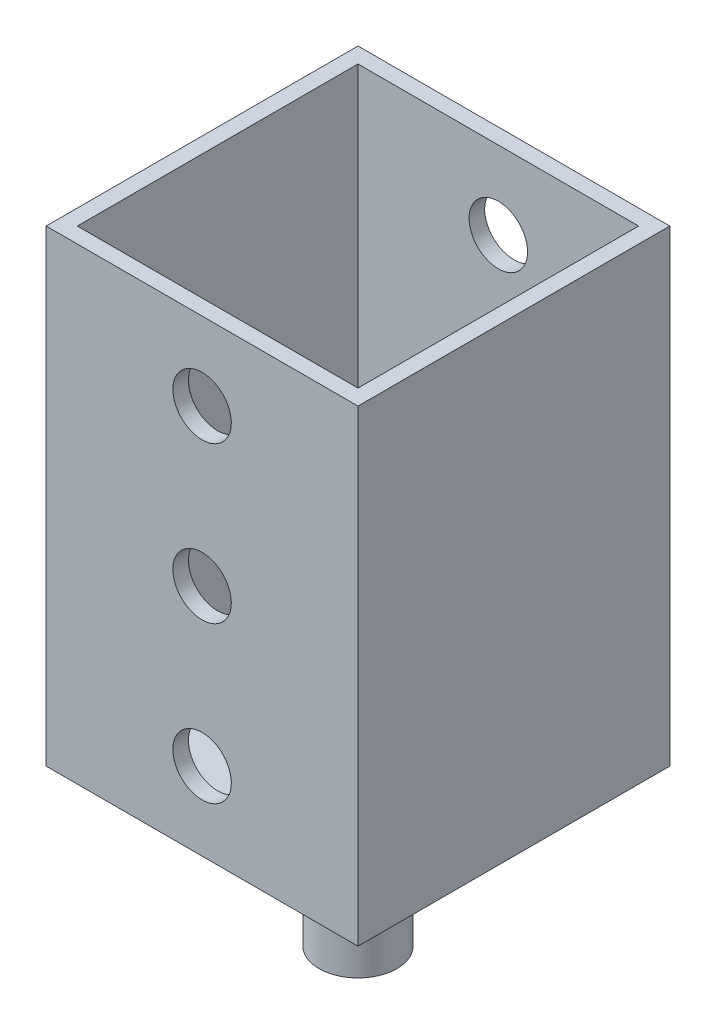
SolidWorks part; units mm, degrees
ref_plane "Front Plane" through (0, 0, 0) normal (0, 0, 1) x (1, 0, 0)
ref_plane "Top Plane" through (0, 0, 0) normal (0, 1, 0) x (1, 0, 0)
ref_plane "Right Plane" through (0, 0, 0) normal (1, 0, 0) x (0, 0, -1)
sketch "Sketch1" plane through (0, 0, 0) normal (0, 0, 1) x (1, 0, 0)
  line L1 (0, 0) -> (50.8, 0)
  line L2 (0, 0) -> (0, 76.2)
  line L3 (0, 76.2) -> (50.8, 76.2)
  line L4 (50.8, 0) -> (50.8, 76.2)
  dimension "D1" = 76.2
  dimension "D2" = 50.8
extrude "Boss-Extrude1" add sketch "Sketch1" along normal mid plane 50.8
sketch "Sketch2" plane through (0, 0, 25.4) normal (0, 0, 1) x (1, 0, 0)
  line L0 (0, 0) -> (50.8, 0) construction
  line L1 (0, 76.2) -> (0, 0) construction
  circle A1 centre (25.4, 38.1) radius 4.7625
  circle A2 centre (25.4, 63.5) radius 4.7625
  circle A3 centre (25.4, 88.9) radius 3.175
  circle A4 centre (25.4, 12.7) radius 4.7625
  dimension "D1" = 25.4
  dimension "D2" = 9.525
  dimension "D3" = 9.525
  dimension "D4" = 6.35
  dimension "D5" = 12.7
  dimension "D9" = 9.525
  dimension "D6" = 25.4
  dimension "D7" = 25.4
  dimension "D8" = 25.4
extrude "Cut-Extrude1" cut sketch "Sketch2" against normal through all
sketch "Sketch3" plane through (0, 76.2, 0) normal (0, 1, 0) x (1, 0, 0)
  line L0 (0, -25.4) -> (0, 25.4) construction
  line L1 (2.54, -22.86) -> (48.26, -22.86)
  line L2 (2.54, -22.86) -> (2.54, 22.86)
  line L3 (2.54, 22.86) -> (48.26, 22.86)
  line L4 (48.26, -22.86) -> (48.26, 22.86)
  line L5 (50.8, -25.4) -> (0, -25.4) construction
  dimension "D1" = 45.72
  dimension "D2" = 45.72
  dimension "D3" = 2.54
  dimension "D4" = 2.54
extrude "Cut-Extrude2" cut sketch "Sketch3" against normal blind 73.66
sketch "Sketch4" plane through (0, 0, 0) normal (0, -1, 0) x (1, 0, 0)
  line L0 (0, 25.4) -> (50.8, 25.4) construction
  line L1 (0, 25.4) -> (0, -25.4) construction
  circle A0 centre (25.4, 0) radius 6.35
  dimension "D1" = 25.4
  dimension "D2" = 25.4
extrude "Boss-Extrude2" add sketch "Sketch4" along normal blind 25.4
